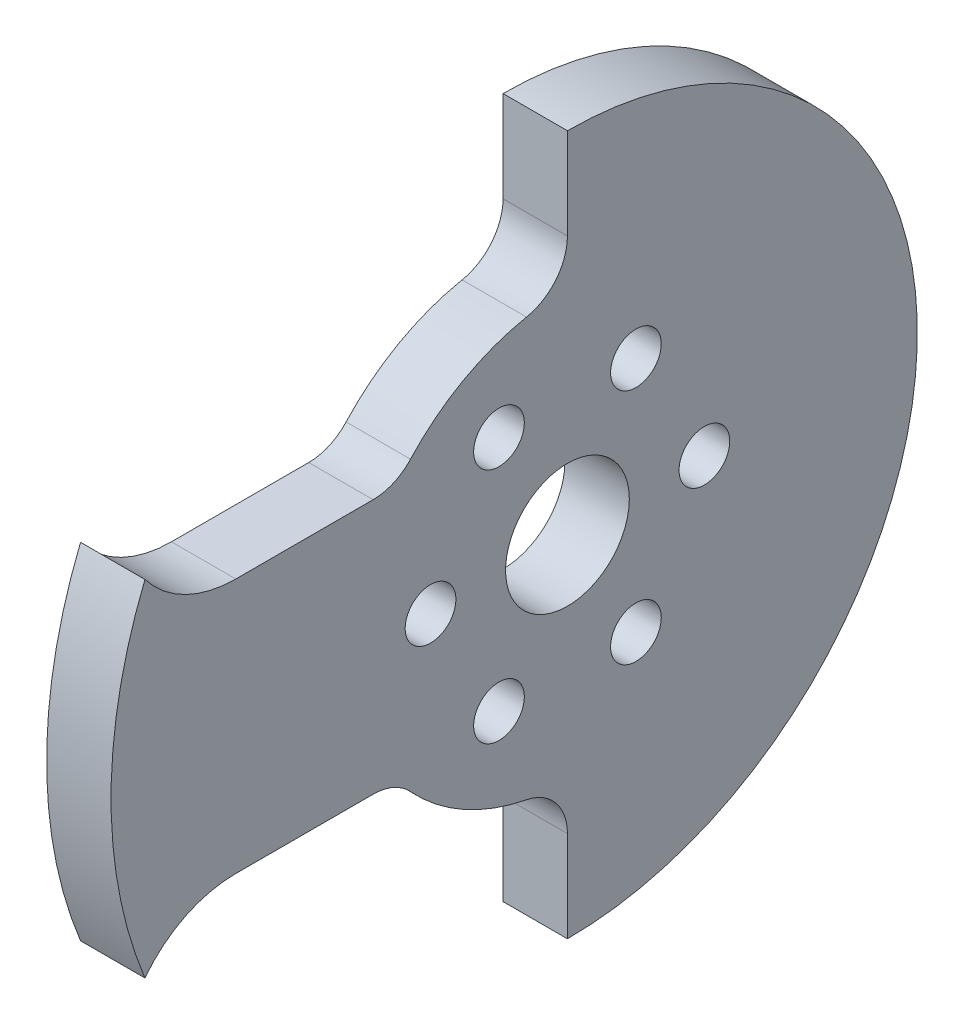
SolidWorks part; units mm, degrees
material "Alloy Steel"
ref_plane "Front Plane" through (0, 0, 0) normal (0, 0, 1) x (1, 0, 0)
ref_plane "Top Plane" through (0, 0, 0) normal (0, 1, 0) x (1, 0, 0)
ref_plane "Right Plane" through (0, 0, 0) normal (1, 0, 0) x (0, 0, -1)
other "Center of Mass"
sketch "Sketch1" plane through (0, 0, 0) normal (1, 0, 0) x (0, 0, -1)
  line L0 (20.5692, 47) -> (-3.4308, 47) construction
  line L1 (55.0692, 47) -> (48.3192, 58.6913) construction
  line L2 (48.3192, 58.6913) -> (34.8192, 58.6913) construction
  line L3 (34.8192, 58.6913) -> (28.0692, 47) construction
  line L4 (28.0692, 47) -> (34.8192, 35.3087) construction
  line L5 (34.8192, 35.3087) -> (48.3192, 35.3087) construction
  line L6 (48.3192, 35.3087) -> (55.0692, 47) construction
  line L7 (-0.0899, 64.0152) -> (-0.0286, 63.9362)
  line L8 (-0.0899, 64.0152) -> (-0.1277, 63.9226) construction
  line L9 (8.8703, 59.575) -> (22.4089, 59.575)
  line L10 (8.8703, 34.425) -> (22.4089, 34.425)
  line L11 (-0.0899, 29.9848) -> (-0.0286, 30.0638)
  line L12 (41.5692, 72.5147) -> (41.5692, 81.5)
  line L13 (41.5692, 21.4853) -> (41.5692, 12.5)
  line L14 (41.5692, -953) -> (41.5692, 49047) construction
  circle A0 centre (41.5692, 47) radius 45 construction
  circle A1 centre (41.5692, 47) radius 45 construction
  circle A2 centre (41.5692, 47) radius 6 construction
  circle A3 centre (41.5692, 47) radius 6.1
  circle A4 centre (41.5692, 47) radius 21 construction
  circle A5 centre (41.5692, 47) radius 11.6913 construction
  circle A6 centre (48.3192, 58.6913) radius 2.5
  circle A7 centre (48.3192, 58.6913) radius 7.5 construction
  circle A8 centre (34.8192, 58.6913) radius 2.5
  circle A9 centre (28.0692, 47) radius 2.5
  circle A10 centre (34.8192, 35.3087) radius 2.5
  circle A11 centre (48.3192, 35.3087) radius 2.5
  circle A12 centre (55.0692, 47) radius 2.5
  arc A13 (-0.0899, 64.0152) -> (-0.0899, 29.9848) centre (41.5692, 47) ccw
  arc A14 (-0.0286, 63.9362) -> (8.8703, 59.575) centre (8.8703, 70.8346) ccw
  arc A15 (22.4089, 59.575) -> (26.0935, 61.1952) centre (22.4089, 64.575) ccw
  arc A16 (22.4089, 34.425) -> (26.0935, 32.8048) centre (22.4089, 29.425) cw
  arc A17 (-0.0286, 30.0638) -> (8.8703, 34.425) centre (8.8703, 23.1654) cw
  circle A18 centre (41.5692, 47) radius 21.3961 construction
  circle A19 centre (41.5692, 47) radius 21.3961 construction
  arc A20 (41.5692, 81.5) -> (41.5692, 12.5) centre (41.5692, 47) cw
  arc A21 (41.5692, 72.5147) -> (37.5308, 67.608) centre (36.5692, 72.5147) cw
  arc A22 (37.5308, 67.608) -> (26.0935, 61.1952) centre (41.5692, 47) ccw
  arc A23 (37.5308, 26.392) -> (26.0935, 32.8048) centre (41.5692, 47) cw
  arc A24 (41.5692, 21.4853) -> (37.5308, 26.392) centre (36.5692, 21.4853) ccw
  point P39 (41.5692, 92)
  dimension "D1" = 12
  dimension "D2" = 0.1
  dimension "D3" = 5
  dimension "D4" = 27
  dimension "D9" = 5
  dimension "D10" = 34.5
  dimension "D5" = 0.1
  dimension "D6" = 60
  dimension "D7" = 25.15
  dimension "D8" = 10
  dimension "D11" = 10.5
extrude "Boss-Extrude1" add sketch "Sketch1" along normal blind 3.175 and the other way blind 3.175
ref_axis "Axis1" through (3.175, 47, -41.5692) along (-1, 0, 0)
